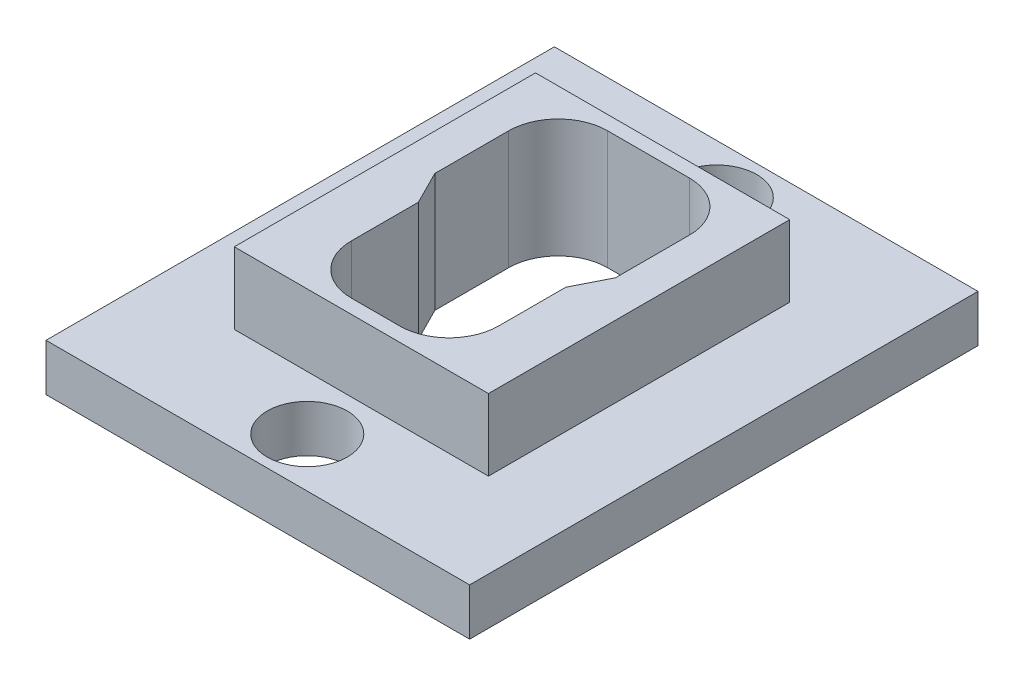
SolidWorks part; units mm, degrees
ref_plane "Front Plane" through (0, 0, 0) normal (0, 0, 1) x (1, 0, 0)
ref_plane "Top Plane" through (0, 0, 0) normal (0, 1, 0) x (1, 0, 0)
ref_plane "Right Plane" through (0, 0, 0) normal (1, 0, 0) x (0, 0, -1)
sketch "Sketch1" plane through (0, 0, 0) normal (0, 1, 0) x (1, 0, 0)
  line L0 (0, 0) -> (0, 13.716) construction
  line L1 (2.2087, 6.604) -> (-2.2087, 6.604)
  line L2 (0, 0) -> (13.208, 0) construction
  line L3 (-4.1137, 4.699) -> (-4.1137, 0.8928)
  line L4 (0, 0) -> (0, -13.208) construction
  line L5 (0, -6.604) -> (-1.3081, -6.604)
  line L6 (-3.2131, -4.699) -> (-3.2131, -0.8928)
  line L7 (-4.1137, 0.8928) -> (-3.2131, -0.8928)
  line L8 (4.1137, 0.8928) -> (3.2131, -0.8928)
  line L9 (4.1137, 4.699) -> (4.1137, 0.8928)
  line L10 (3.2131, -4.699) -> (3.2131, -0.8928)
  line L11 (0, -6.604) -> (1.3081, -6.604)
  line L12 (-11.43, 13.716) -> (11.43, 13.716)
  line L13 (11.43, 13.716) -> (11.43, -13.716)
  line L14 (11.43, -13.716) -> (-11.43, -13.716)
  line L15 (-11.43, 13.716) -> (-11.43, -13.716)
  arc A1 (-2.2087, 6.604) -> (-4.1137, 4.699) centre (-2.2087, 4.699) ccw
  arc A2 (-1.3081, -6.604) -> (-3.2131, -4.699) centre (-1.3081, -4.699) cw
  arc A3 (2.2087, 6.604) -> (4.1137, 4.699) centre (2.2087, 4.699) cw
  arc A4 (1.3081, -6.604) -> (3.2131, -4.699) centre (1.3081, -4.699) ccw
  point P17 (0, 6.858)
  point P27 (0, -13.716)
  dimension "D3" = 1.905
  dimension "D4" = 1.905
  dimension "D5" = 11.43
  dimension "D1" = 6.604
  dimension "D2" = 6.604
  dimension "D6" = 13.716
  dimension "D7" = 13.716
extrude "Boss-Extrude2" add sketch "Sketch1" along normal blind 6.4008
sketch "Sketch4" plane through (0, 6.4008, 0) normal (0, 1, 0) x (1, 0, 0)
  line L0 (0, 0) -> (11.43, 0) construction
  line L1 (11.43, -13.716) -> (11.43, 13.716) construction
  circle A0 centre (0, 11.049) radius 2.159
  circle A1 centre (0, -11.049) radius 2.159
  point P2 (0, -11.049)
  dimension "D1" = 11.049
sketch "Sketch5" plane through (0, 6.4008, 0) normal (0, 1, 0) x (1, 0, 0)
  line L0 (0, 0) -> (11.1665, 0) construction
  line L1 (0, 0) -> (0, 13.716) construction
  line L2 (6.858, -8.128) -> (6.858, 8.128)
  line L3 (-6.858, 8.128) -> (6.858, 8.128)
  line L4 (-6.858, -8.128) -> (-6.858, 8.128)
  line L5 (-11.43, 13.716) -> (11.43, 13.716)
  line L6 (-11.43, 13.716) -> (-11.43, -13.716)
  line L7 (-11.43, -13.716) -> (11.43, -13.716)
  line L8 (11.43, 13.716) -> (11.43, -13.716)
  line L9 (-6.858, -8.128) -> (6.858, -8.128)
  point P13 (0, -8.128)
  point P14 (0, 8.128)
  point P16 (6.858, 0)
  point P17 (-6.858, 0)
extrude "Cut-Extrude2" cut sketch "Sketch4" against normal through all both and the other way through all
extrude "Cut-Extrude3" cut sketch "Sketch5" against normal blind 3.8608
sketch "Sketch6" plane through (0, 6.4008, 0) normal (0, 1, 0) x (1, 0, 0)
  line L0 (-3.2131, -0.8928) -> (-3.2131, -4.699) construction
  line L1 (-1.3081, -6.604) -> (1.3081, -6.604) construction
  line L2 (3.2131, -4.699) -> (3.2131, -0.8928) construction
  line L3 (3.2131, -0.8928) -> (4.1137, 0.8928) construction
  line L4 (4.1137, 0.8928) -> (4.1137, 4.699) construction
  line L5 (2.2087, 6.604) -> (-2.2087, 6.604) construction
  line L6 (-4.1137, 4.699) -> (-4.1137, 0.8928) construction
  line L7 (-4.1137, 0.8928) -> (-3.2131, -0.8928) construction
  line L8 (-3.2131, -0.8928) -> (-3.2131, -4.699) construction
  line L9 (-1.3081, -6.604) -> (1.3081, -6.604) construction
  line L10 (3.2131, -4.699) -> (3.2131, -0.8928) construction
  line L11 (3.2131, -0.8928) -> (4.1137, 0.8928) construction
  line L12 (4.1137, 0.8928) -> (4.1137, 4.699) construction
  line L13 (2.2087, 6.604) -> (-2.2087, 6.604) construction
  line L14 (-4.1137, 4.699) -> (-4.1137, 0.8928) construction
  line L15 (-4.1137, 0.8928) -> (-3.2131, -0.8928) construction
  line L16 (-3.9751, -1.0741) -> (-3.9751, -4.699)
  line L17 (-1.3081, -7.366) -> (1.3081, -7.366)
  line L18 (3.9751, -4.699) -> (3.9751, -1.0741)
  line L19 (3.9751, -1.0741) -> (4.8757, 0.7115)
  line L20 (4.8757, 0.7115) -> (4.8757, 4.699)
  line L21 (2.2087, 7.366) -> (-2.2087, 7.366)
  line L22 (-4.8757, 4.699) -> (-4.8757, 0.7115)
  line L23 (-4.8757, 0.7115) -> (-3.9751, -1.0741)
  arc A0 (-3.2131, -4.699) -> (-1.3081, -6.604) centre (-1.3081, -4.699) ccw construction
  arc A1 (1.3081, -6.604) -> (3.2131, -4.699) centre (1.3081, -4.699) ccw construction
  arc A2 (4.1137, 4.699) -> (2.2087, 6.604) centre (2.2087, 4.699) ccw construction
  arc A3 (-2.2087, 6.604) -> (-4.1137, 4.699) centre (-2.2087, 4.699) ccw construction
  arc A4 (-3.2131, -4.699) -> (-1.3081, -6.604) centre (-1.3081, -4.699) ccw construction
  arc A5 (1.3081, -6.604) -> (3.2131, -4.699) centre (1.3081, -4.699) ccw construction
  arc A6 (4.1137, 4.699) -> (2.2087, 6.604) centre (2.2087, 4.699) ccw construction
  arc A7 (-2.2087, 6.604) -> (-4.1137, 4.699) centre (-2.2087, 4.699) ccw construction
  arc A8 (-3.9751, -4.699) -> (-1.3081, -7.366) centre (-1.3081, -4.699) ccw
  arc A9 (1.3081, -7.366) -> (3.9751, -4.699) centre (1.3081, -4.699) ccw
  arc A10 (4.8757, 4.699) -> (2.2087, 7.366) centre (2.2087, 4.699) ccw
  arc A11 (-2.2087, 7.366) -> (-4.8757, 4.699) centre (-2.2087, 4.699) ccw
  dimension "D1" = 0.762
extrude "Cut-Extrude4" cut sketch "Sketch6" against normal through all both and the other way through all
